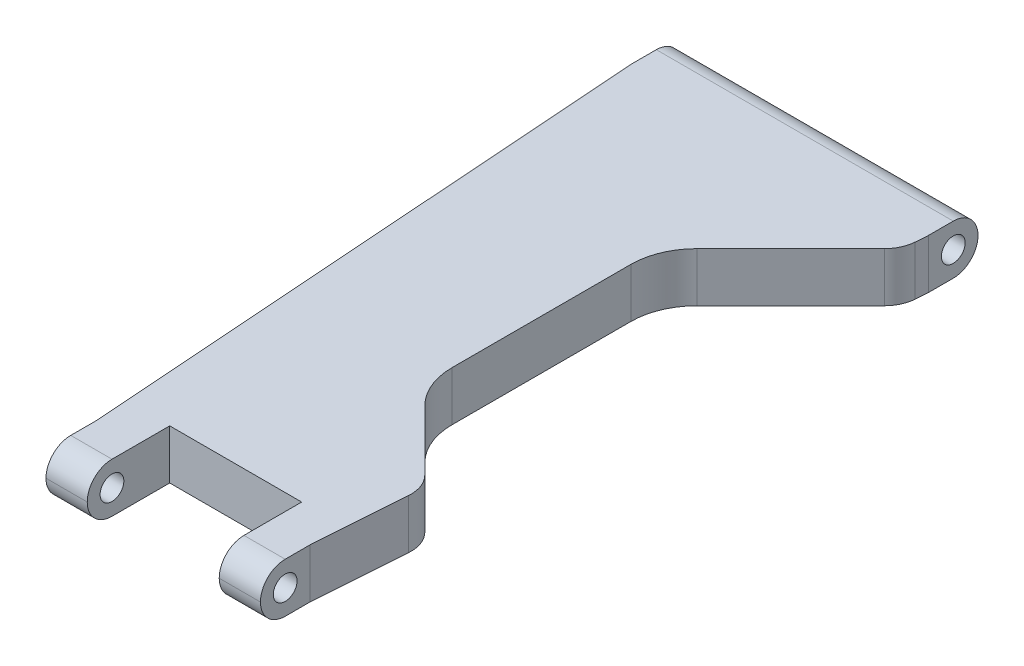
SolidWorks part; units mm, degrees
ref_plane "Front Plane" through (0, 0, 0) normal (0, 0, 1) x (1, 0, 0)
ref_plane "Top Plane" through (0, 0, 0) normal (0, 1, 0) x (1, 0, 0)
ref_plane "Right Plane" through (0, 0, 0) normal (1, 0, 0) x (0, 0, -1)
sketch "Sketch1" plane through (0, 0, 0) normal (0, 1, 0) x (1, 0, 0)
  line L0 (0, 0) -> (0, -120.65) construction
  line L1 (-28.575, 0) -> (28.575, 0) construction
  line L2 (-28.575, 4.7625) -> (-28.575, -4.7625)
  line L3 (28.575, 4.7625) -> (28.575, -4.7625)
  line L4 (-20.6375, -120.65) -> (20.6375, -120.65) construction
  line L5 (-20.6375, -115.8875) -> (-20.6375, -125.4125)
  line L6 (20.6375, -115.8875) -> (20.6375, -125.4125)
  line L7 (-28.575, -4.7625) -> (-20.6375, -115.8875)
  line L8 (28.575, -4.7625) -> (20.6375, -115.8875)
  line L9 (-20.6375, -125.4125) -> (20.6375, -125.4125)
  line L11 (-12.7, -125.4125) -> (-12.7, -109.5375)
  line L12 (-12.7, -109.5375) -> (12.7, -109.5375)
  line L13 (-28.575, 4.7625) -> (28.575, 4.7625)
  line L14 (-28.575, -4.7625) -> (28.575, -4.7625)
  line L15 (-20.6375, -115.8875) -> (20.6375, -115.8875)
  line L16 (-19.05, 4.7625) -> (-19.05, -4.7625)
  line L17 (-19.05, -4.7625) -> (19.05, -4.7625)
  line L18 (19.05, -4.7625) -> (19.05, 4.7625)
  line L19 (12.7, -109.5375) -> (12.7, -125.4125)
  line L23 (28.2348, -9.525) -> (4.7625, -32.9973)
  line L24 (4.7625, -32.9973) -> (4.7625, -77.9009)
  line L25 (4.7625, -77.9009) -> (22.1116, -95.25)
  point P6 (0, 0)
  point P9 (-28.575, 0)
  point P11 (28.575, 0)
  point P16 (0, -120.65)
  point P18 (-20.6375, -120.65)
  point P21 (20.6375, -120.65)
  dimension "D1" = 9.525
  dimension "D2" = 57.15
  dimension "D3" = 9.525
  dimension "D4" = 41.275
  dimension "D5" = 120.65
  dimension "D6" = 7.9375
  dimension "D7" = 7.9375
  dimension "D8" = 9.525
  dimension "D9" = 9.525
  dimension "D10" = 15.875
  dimension "D13" = 9.525
  dimension "D14" = 9.525
  dimension "D15" = 25.4
  dimension "D16" = 45
  dimension "D17" = 45
extrude "Boss-Extrude1" add sketch "Sketch1" along normal blind 9.525 contours L16 L13 L2 L14 | L18 L14 L3 L13 | L7 L15 L8 L14 | L15 L5 L9 | L15 L19 L9 L6 | L14 L18 L13 L16 region at (-23.8125, 0, 0) region at (-5.339, 0, 56.6599) region at (0, 0, 0) region at (-16.6687, 0, 120.65) region at (23.8125, 0, 0) region at (16.6687, 0, 120.65)
sketch "Sketch6" plane through (-28.575, 0, 0) normal (-1, 0, 0) x (0, 0, 1)
  line L0 (-4.7625, 9.525) -> (-4.7625, 0) construction
  line L1 (115.8875, 9.525) -> (125.4125, 9.525) construction
  circle A0 centre (0, 4.7625) radius 2.286
  circle A1 centre (120.65, 4.7625) radius 2.286
  point P2 (-4.7625, 4.7625)
  point P3 (0, 0)
  point P10 (120.65, 9.525)
  dimension "D1" = 4.572
extrude "Cut-Extrude2" cut sketch "Sketch6" against normal through all both and the other way through all
fillet "Fillet5" radius 4.7625 6 edges at (0, 0, -4.7625) (0, 9.525, -4.7625) (16.6687, 0, 125.4125) (-16.6687, 0, 125.4125) (-16.6687, 9.525, 125.4125) (16.6687, 9.525, 125.4125)
fillet "Fillet6" radius 12.7 2 edges at (4.7625, 4.7625, 77.9009) (4.7625, 4.7625, 32.9973)
fillet "Fillet7" radius 6.35 2 edges at (28.2348, 4.7625, 9.525) (22.1116, 4.7625, 95.25)
